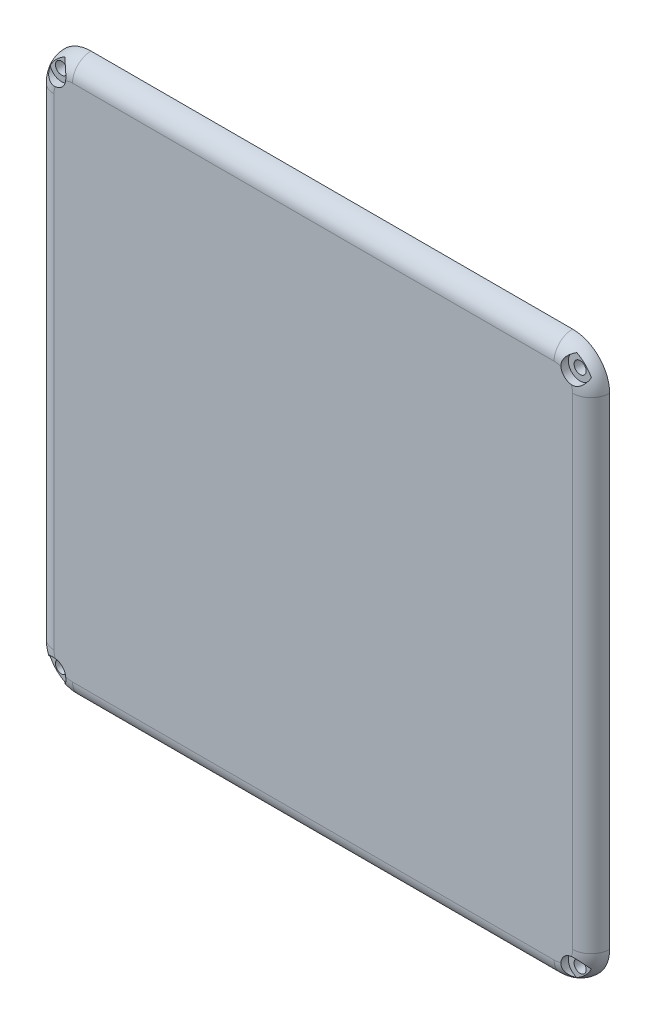
SolidWorks part; units mm, degrees
ref_plane "Alzado" through (0, 0, 0) normal (0, 0, 1) x (1, 0, 0)
ref_plane "Planta" through (0, 0, 0) normal (0, 1, 0) x (1, 0, 0)
ref_plane "Vista lateral" through (0, 0, 0) normal (1, 0, 0) x (0, 0, -1)
sketch "Croquis1" plane through (0, 0, 0) normal (0, 0, 1) x (1, 0, 0)
  line L1 (-75, 75) -> (75, 75)
  line L2 (-75, 75) -> (-75, -75)
  line L3 (-75, -75) -> (75, -75)
  line L4 (75, 75) -> (75, -75)
  line L5 (-75, 75) -> (75, -75) construction
  line L6 (-75, -75) -> (75, 75) construction
  point P0 (0, 0)
  dimension "D1" = 150
  dimension "D2" = 150
extrude "Saliente-Extruir1" add sketch "Croquis1" along normal blind 5
sketch "Croquis2" plane through (0, 0, 5) normal (0, 0, 1) x (1, 0, 0)
  line L0 (-75, -75) -> (75, -75) construction
  line L1 (75, -75) -> (0, -75) construction
  line L2 (0, -75) -> (0, 75) construction
  line L3 (75, 75) -> (-75, 75) construction
  line L5 (-36, 51) -> (36, 51)
  line L6 (-36, 51) -> (-36, -51)
  line L7 (-36, -51) -> (36, -51)
  line L8 (36, 51) -> (36, -51)
  line L9 (-36, 51) -> (36, -51) construction
  line L10 (-36, -51) -> (36, 51) construction
  point P8 (0, 0)
  dimension "D1" = 102
  dimension "72" = 72
sketch "Croquis3" plane through (0, 0, 5) normal (0, 0, 1) x (1, 0, 0)
  line L1 (-2.5, 37.5) -> (2.5, 37.5)
  line L2 (-2.5, 37.5) -> (-2.5, -37.5)
  line L3 (-2.5, -37.5) -> (2.5, -37.5)
  line L4 (2.5, 37.5) -> (2.5, -37.5)
  line L5 (-2.5, 37.5) -> (2.5, -37.5) construction
  line L6 (-2.5, -37.5) -> (2.5, 37.5) construction
  point P0 (0, 0)
  dimension "D1" = 75
  dimension "D2" = 5
fillet "Redondeo1" radius 10 4 edges at (75, 75, 2.5) (-75, 75, 2.5) (-75, -75, 2.5) (75, -75, 2.5)
fillet "Redondeo3" radius 5 8 edges at (72.0711, 72.0711, 5) (75, 0, 5) (72.0711, -72.0711, 5) (0, -75, 5) (-72.0711, -72.0711, 5) (-75, 0, 5) (-72.0711, 72.0711, 5) (0, 75, 5)
sketch "Croquis6" plane through (0, 0, 5) normal (0, 0, 1) x (1, 0, 0)
  line L0 (0, 0) -> (70, 0) construction
  line L1 (70, -65) -> (70, 65) construction
  line L2 (70, 0) -> (-70, 0) construction
  line L3 (-70, 65) -> (-70, -65) construction
  line L5 (-70, -70) -> (70, -70)
  line L6 (-70, -70) -> (-70, 70)
  line L7 (-70, 70) -> (70, 70)
  line L8 (70, -70) -> (70, 70)
  line L9 (-70, -70) -> (70, 70) construction
  line L10 (-70, 70) -> (70, -70) construction
  dimension "D1" = 140
  dimension "D2" = 140
hole_wizard "Refrentado para tornillo con cabeza troncocónica de #41" positions "Croquis10" profile "Croquis11" counterbore size "#4" standard "Ansi Inch"
sketch "Croquis10" plane through (0, 0, 5) normal (0, 0, 1) x (1, 0, 0)
  point P0 (-70, 70)
  point P3 (-70, -70)
  point P6 (70, -70)
  point P9 (70, 70)
sketch "Croquis11" plane through (-70, 70, 5) normal (1, 0, 0) x (0, -1, 0)
  line L0 (0, 0) -> (0, 50.9806)
  line L1 (0, 50.9806) -> (1.6319, 50)
  line L2 (1.6319, 50) -> (1.6319, 2.032)
  line L3 (1.6319, 2.032) -> (3.175, 2.032)
  line L4 (3.175, 2.032) -> (3.175, 0)
  line L5 (3.175, 0) -> (0, 0)
  line L10 (0, 50.9806) -> (-1.632, 50) construction
  line L11 (0, -6.35) -> (0, 107.95) construction
  dimension "Diámetro de taladro" = 3.2639
  dimension "Profundidad de taladro" = 50
  dimension "Diámetro de refrentado" = 6.35
  dimension "Profundidad de refrentado" = 2.032
  dimension "Ángulo de perforador" = 118
